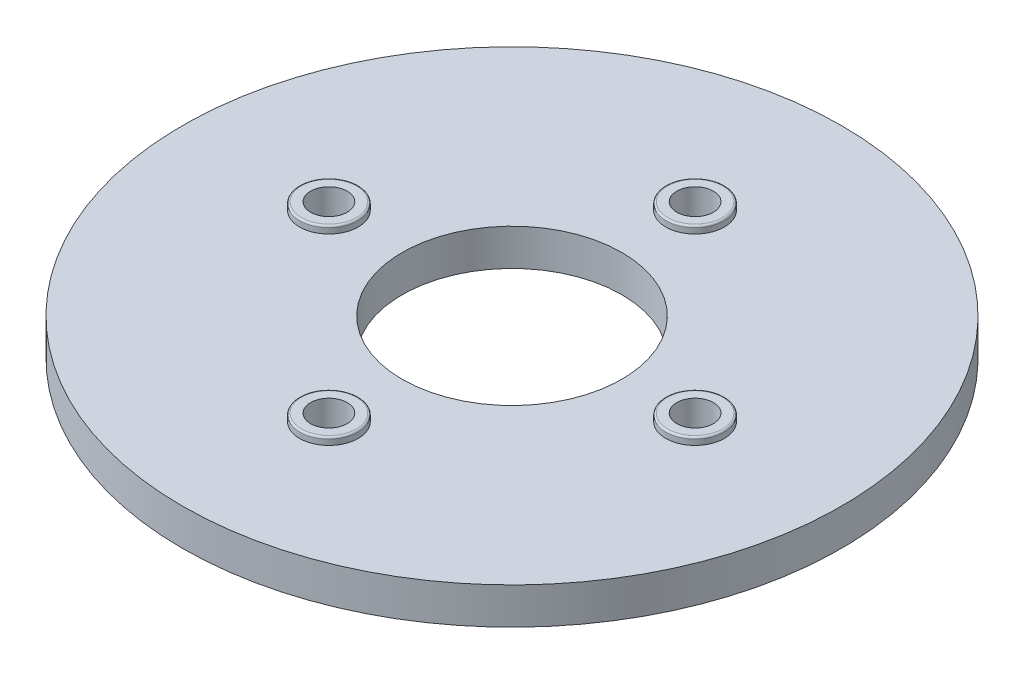
SolidWorks part; units mm, degrees
ref_plane "Front Plane" through (0, 0, 0) normal (0, 0, 1) x (1, 0, 0)
ref_plane "Top Plane" through (0, 0, 0) normal (0, 1, 0) x (1, 0, 0)
ref_plane "Right Plane" through (0, 0, 0) normal (1, 0, 0) x (0, 0, -1)
sketch "Sketch1" plane through (0, 0, 0) normal (0, 1, 0) x (1, 0, 0)
  circle A0 centre (0, 0) radius 45
  circle A1 centre (0, 0) radius 15
  circle A2 centre (0, 0) radius 25
  circle A3 centre (0, 25) radius 2.5
  circle A4 centre (25, 0) radius 2.5
  circle A5 centre (0, -25) radius 2.5
  circle A6 centre (-25, 0) radius 2.5
  point P16 (0, 0)
  dimension "D1" = 90
  dimension "D2" = 30
  dimension "D3" = 50
  dimension "D4" = 5
  dimension "D5" = 4
extrude "Boss-Extrude1" add sketch "Sketch1" along normal blind 5 contours A0 A6 A2 A3 A4 A5 | A6 A2 A5 A4 A3 A1 region at (-43.7272, 0, 0) region at (21.7964, 0, 0)
sketch "Sketch2" plane through (0, 5, 0) normal (0, 1, 0) x (1, 0, 0)
  circle A0 centre (0, 0) radius 25
  circle A1 centre (0, 25) radius 4
  circle A2 centre (0, 25) radius 2.5
  circle A3 centre (25, 0) radius 2.5
  circle A4 centre (25, 0) radius 4
  circle A5 centre (0, -25) radius 2.5
  circle A6 centre (0, -25) radius 4
  circle A7 centre (-25, 0) radius 2.5
  circle A8 centre (-25, 0) radius 4
  point P19 (0, 0)
  circle M1 centre (-25, 0) radius 2.5
  circle M2 centre (0, 25) radius 2.5
  circle M3 centre (25, 0) radius 2.5
  circle M4 centre (0, -25) radius 2.5
  dimension "D1" = 8
  dimension "D2" = 5
  dimension "D3" = 4
extrude "Boss-Extrude2" add sketch "Sketch2" along normal blind 1 contours A0 A8 M1 | A0 A8 M1 | A0 A6 M4 | A0 A6 M4 | A0 A4 M3 | A0 A4 M3 | A0 A1 M2 | A0 A1 M2 region at (22.4113, 5, 0) region at (24.8789, 5, -3.2553) region at (0, 5, -21.0887) region at (3.2553, 5, -24.8789) region at (3.9059, 5, 24.8435) region at (3.232, 5, 24.7008) region at (-22.1258, 5, -2.6528) region at (-24.8789, 5, -3.2553)
fillet "Fillet1" radius 0.25 4 edges at (25, 6, 4) (0, 6, 29) (-25, 6, 4) (0, 6, -21)
